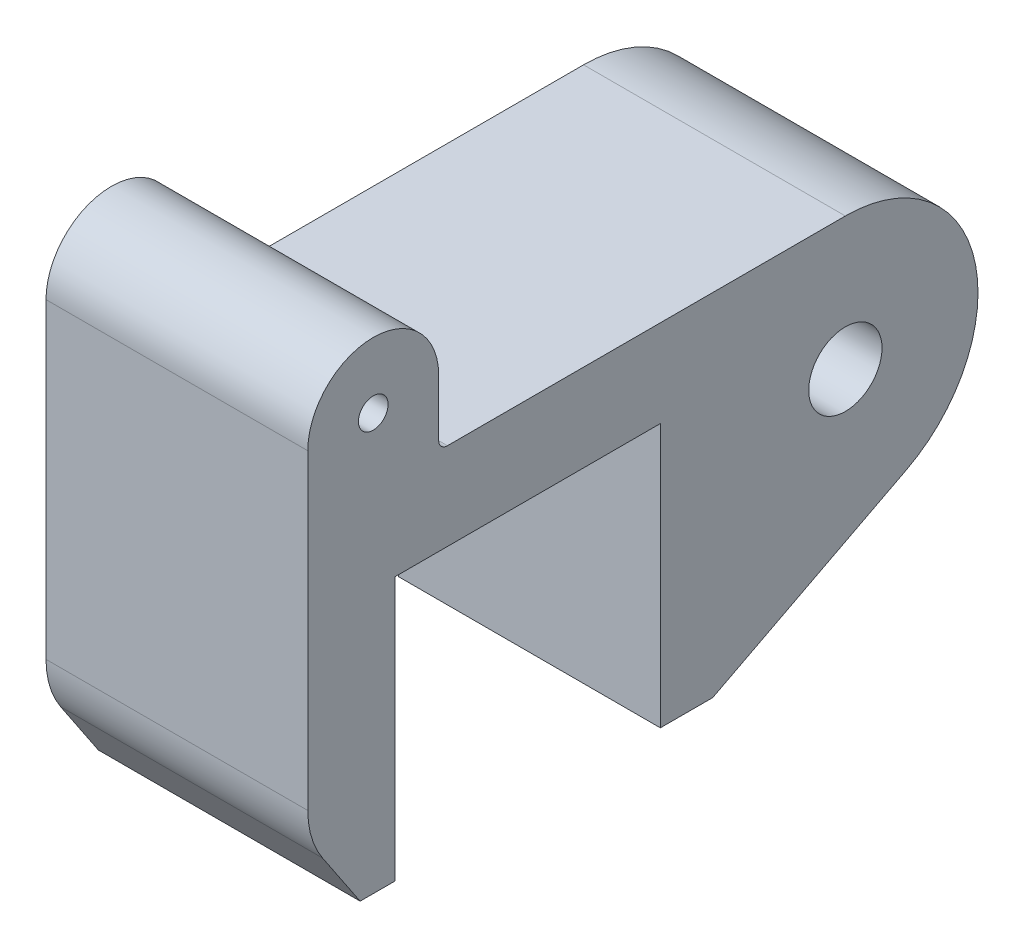
SolidWorks part; units mm, degrees
ref_plane "Front Plane" through (0, 0, 0) normal (1, 0, 0) x (0, 1, 0)
ref_plane "Top Plane" through (0, 0, 0) normal (0, 0, 1) x (0, 1, 0)
ref_plane "Right Plane" through (0, 0, 0) normal (0, 1, 0) x (-1, 0, 0)
sketch "Sketch1" plane through (0, 0, 0) normal (1, 0, 0) x (0, 1, 0)
  line L0 (-30.2, 0) -> (0, 0)
  line L1 (0, 0) -> (0, 30.4)
  line L2 (-30.2, 0) -> (-30.2, -6)
  line L3 (0, 30.4) -> (-30.2, 30.4)
  line L4 (-30.2, 30.4) -> (-30.2, 34.4)
  line L5 (-30.2, 34.4) -> (-23.7635, 38.7095)
  line L6 (10, -21.2) -> (10, 24.4)
  line L7 (-30.2, -6) -> (-18.6947, -28.1952)
  line L8 (-18.2, 40.4) -> (17.5, 40.4)
  line L9 (-5.2, -6) -> (31.843, -6) construction
  line L10 (17.5, 25.4) -> (11, 25.4)
  line L11 (10, 24.4) -> (10, 32.9) construction
  circle A0 centre (-5.2, -21.2) radius 4.2
  circle A1 centre (-5.2, -21.2) radius 15.2
  arc A2 (-23.7635, 38.7095) -> (-18.2, 40.4) centre (-18.2, 30.4) cw
  circle A3 centre (17.5, 32.9) radius 1.7
  circle A4 centre (17.5, 32.9) radius 7.5
  arc A5 (11, 25.4) -> (10, 24.4) centre (11, 24.4) ccw
  point P20 (17.5, 25.4)
  point P24 (10, 32.9)
  dimension "D3" = 8.4
  dimension "D4" = 30.4
  dimension "D10" = 3.4
  dimension "D11" = 15
  dimension "D13" = 1
  dimension "D14" = 10
  dimension "D1" = 30.4
  dimension "D2" = 30.2
  dimension "D5" = 21.2
  dimension "D6" = 10
  dimension "D7" = 6
  dimension "D9" = 4
  dimension "D8" = 30.4
  dimension "D12" = 12
extrude "Boss-Extrude1" add sketch "Sketch1" along normal mid plane 30 contours A1 A0 | A5 L10 A4 L8 A2 L5 L4 L3 L1 L0 L2 L7 A1 L6 | A4 A3 region at (0, -15.1, -0.8355) region at (0, -8.6982, -6.8502) region at (0, 10.2121, 32.9)
equation "\"D5@Sketch1\"=\"D4@Sketch1\"/2+6"
